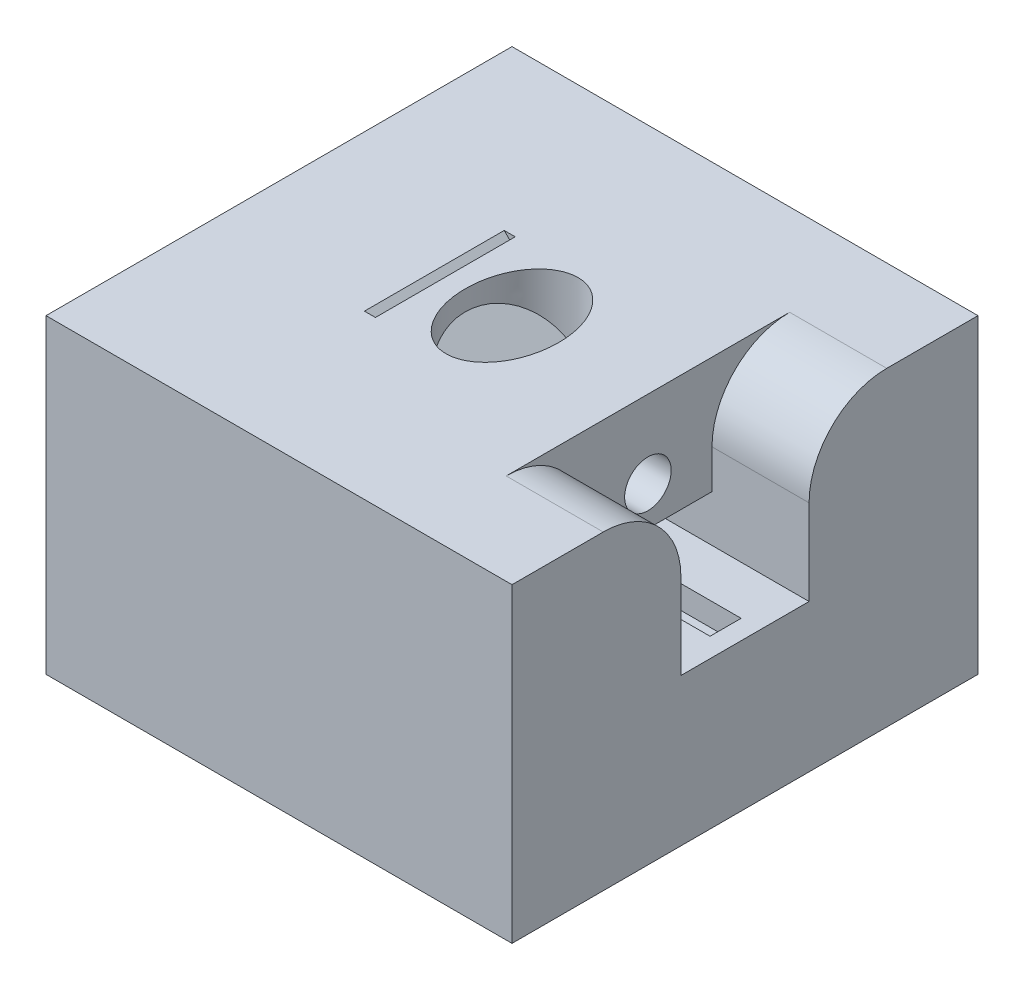
SolidWorks part; units mm, degrees
ref_plane "Front Plane" through (0, 0, 0) normal (0, 0, 1) x (1, 0, 0)
ref_plane "Top Plane" through (0, 0, 0) normal (0, 1, 0) x (1, 0, 0)
ref_plane "Right Plane" through (0, 0, 0) normal (1, 0, 0) x (0, 0, -1)
sketch "Sketch1" plane through (0, 0, 0) normal (0, 1, 0) x (1, 0, 0)
  line L0 (-30, -30) -> (30, 30) construction
  line L1 (-30, 30) -> (30, 30)
  line L2 (-30, 30) -> (-30, -30)
  line L3 (-30, -30) -> (30, -30)
  line L4 (30, 30) -> (30, -30)
  line L5 (-30, 30) -> (30, -30) construction
  point P4 (0, 0)
  dimension "D1" = 60
  dimension "D2" = 60
extrude "Boss-Extrude1" add sketch "Sketch1" along normal blind 10
sketch "Sketch2" plane through (0, 10, 0) normal (0, 1, 0) x (1, 0, 0)
  line L0 (0, -30) -> (0, 30) construction
  line L1 (-30, -30) -> (30, -30) construction
  line L2 (0, -5.5) -> (0, 5.5) construction
  line L3 (30, 30) -> (-30, 30) construction
sketch "Sketch3" plane through (0, 0, 30) normal (0, 0, 1) x (1, 0, 0)
  line L0 (0, 0) -> (0, 30) construction
  line L1 (0, -5.5) -> (0, 5.5) construction
  dimension "D1" = 30
sketch "Sketch4" plane through (0, 0, -30) normal (0, 0, -1) x (-1, 0, 0)
  line L0 (0, 0) -> (0, 30) construction
sketch3d "3DSketch1"
  line L0 (0, 30, 30) -> (0, 30, -30) construction
ref_plane "Plane1" through (15, 15, 0) normal (0.7071, 0.7071, 0) x (0, 0, -1)
sketch "Sketch5" plane through (0, 10, 0) normal (0, 1, 0) x (1, 0, 0)
  line L0 (-30, -30) -> (30, 30) construction
  line L1 (30, 30) -> (30, -30) construction
  line L2 (30, -30) -> (-30, 30) construction
sketch3d "3DSketch2"
  line L0 (0, 10, 0) -> (0, 30, 0) construction
  line L1 (0, 10, 30) -> (0, 10, -30) construction
  dimension "D1" = 20
sketch "Sketch6" plane through (15, 15, 0) normal (0.7071, 0.7071, 0) x (0, 0, -1)
  line L0 (-30, 21.2132) -> (30, 21.2132) construction
  circle A0 centre (0, 21.2132) radius 8.5
  point P4 (0, 29.7132)
  dimension "D1" = 17
sketch "Sketch7" plane through (0, 10, 0) normal (0, 1, 0) x (1, 0, 0)
  line L0 (0, -30) -> (0, 30) construction
  ellipse E0 centre (0, 0) end of major axis (0, 8.5) minor radius 6.0104
  ellipse E1 centre (0, 0) end of major axis (0, -8.5) minor radius 6.0104 construction
  point P1 (-6.0104, 0)
sketch3d "3DSketch3"
  line L0 (-6.0104, 10, 0) -> (-6.0104, 36.0104, 0) construction
loft "Loft1" add profiles "Sketch6", "Sketch7" connector at (-6.0104, 36.0104, 0) connector at (-6.0104, 10, 0)
sketch "Sketch8" plane through (0, 10, 0) normal (0, 1, 0) x (1, 0, 0)
  line L0 (0, -30) -> (0, 30) construction
  line L2 (-30, 30) -> (30, 30)
  line L3 (-30, 30) -> (-30, -30)
  line L4 (-30, -30) -> (30, -30)
  line L5 (30, 30) -> (30, -30)
  ellipse E0 centre (0, 0) end of major axis (0, 8.5) minor radius 6.0104
  ellipse E1 centre (0, 0) end of major axis (0, 8.5) minor radius 6.0104 construction
extrude "Boss-Extrude2" add sketch "Sketch8" along normal blind 30
sketch "Sketch9" plane through (0, 40, 0) normal (0, 1, 0) x (1, 0, 0)
  circle A0 centre (0, 0) radius 3
extrude "Cut-Extrude1" cut sketch "Sketch9" against normal through all
sketch "Sketch10" plane through (30, 0, 0) normal (1, 0, 0) x (0, 0, -1)
  line L0 (0, 0) -> (0, 30) construction
  circle A0 centre (0, 30) radius 3
extrude "Cut-Extrude2" cut sketch "Sketch10" against normal through all
sketch "Sketch11" plane through (30, 0, 0) normal (1, 0, 0) x (0, 0, -1)
  line L0 (-30, 40) -> (30, 40) construction
  line L1 (-8.25, 40) -> (8.25, 40)
  line L2 (-8.25, 40) -> (-8.25, 19)
  line L3 (-8.25, 19) -> (8.25, 19)
  line L4 (8.25, 40) -> (8.25, 19)
  line L5 (0, 0) -> (0, 40) construction
  line L6 (0, 10) -> (0, 30) construction
  point P9 (0, 19)
  dimension "D1" = 16.5
  dimension "D2" = 11
extrude "Cut-Extrude3" cut sketch "Sketch11" against normal blind 12.5
sketch "Sketch12" plane through (17.5, 0, 0) normal (1, 0, 0) x (0, 0, -1)
  line L0 (8.25, 19) -> (8.25, 40) construction
  line L1 (-8.25, 19) -> (8.25, 19)
  line L2 (-8.25, 19) -> (-8.25, 25)
  line L3 (-8.25, 25) -> (8.25, 25)
  line L4 (8.25, 19) -> (8.25, 25)
  dimension "D1" = 6
extrude "Cut-Extrude4" cut sketch "Sketch12" against normal blind 8.5
sketch "Sketch13" plane through (9, 0, 0) normal (1, 0, 0) x (0, 0, -1)
  line L0 (0, 19) -> (0, 16.449) construction
  line L1 (-8.25, 19) -> (8.25, 19) construction
  line L2 (0, 10) -> (0, 30) construction
  line L3 (-8.25, 19) -> (8.25, 19) construction
  line L4 (-2, 19) -> (2, 19)
  line L5 (-2, 19) -> (-2, 16)
  line L6 (-2, 16) -> (2, 16)
  line L7 (2, 19) -> (2, 16)
  dimension "D1" = 3
  dimension "D2" = 4
extrude "Cut-Extrude5" cut sketch "Sketch13" along normal blind 18.5
fillet "Fillet1" radius 10 2 edges at (23.75, 40, 8.25) (23.75, 40, -8.25)
sketch3d "3DSketch4"
  line L0 (-30, 40, 30) -> (30, 40, 30) construction
  line L1 (30, 40, -30) -> (-30, 40, -30) construction
  line L2 (-10, 40, -30) -> (-10, 40, 30) construction
  point P0 (-10, 40, 30)
  point P1 (-10, 40, -30)
ref_plane "Plane2" through (-25, 25, 0) normal (-0.7071, 0.7071, 0) x (0, 0, 1)
sketch "Sketch14" plane through (-25, 25, 0) normal (-0.7071, 0.7071, 0) x (0, 0, 1)
  line L0 (-9, 21.2132) -> (9, 21.2132) construction
  line L1 (-9, 22.2132) -> (9, 22.2132)
  line L2 (-9, 22.2132) -> (-9, 21.2132)
  line L3 (-9, 21.2132) -> (9, 21.2132)
  line L4 (9, 22.2132) -> (9, 21.2132)
  line L5 (30, 21.2132) -> (-30, 21.2132) construction
  line L6 (0, 21.2132) -> (0, 22.2132) construction
  dimension "D1" = 18
  dimension "D2" = 1
extrude "Cut-Extrude7" cut sketch "Sketch14" against normal up to vertex (14.1421 mm away) and the other way blind 20 up to point (0, 30, 3)
